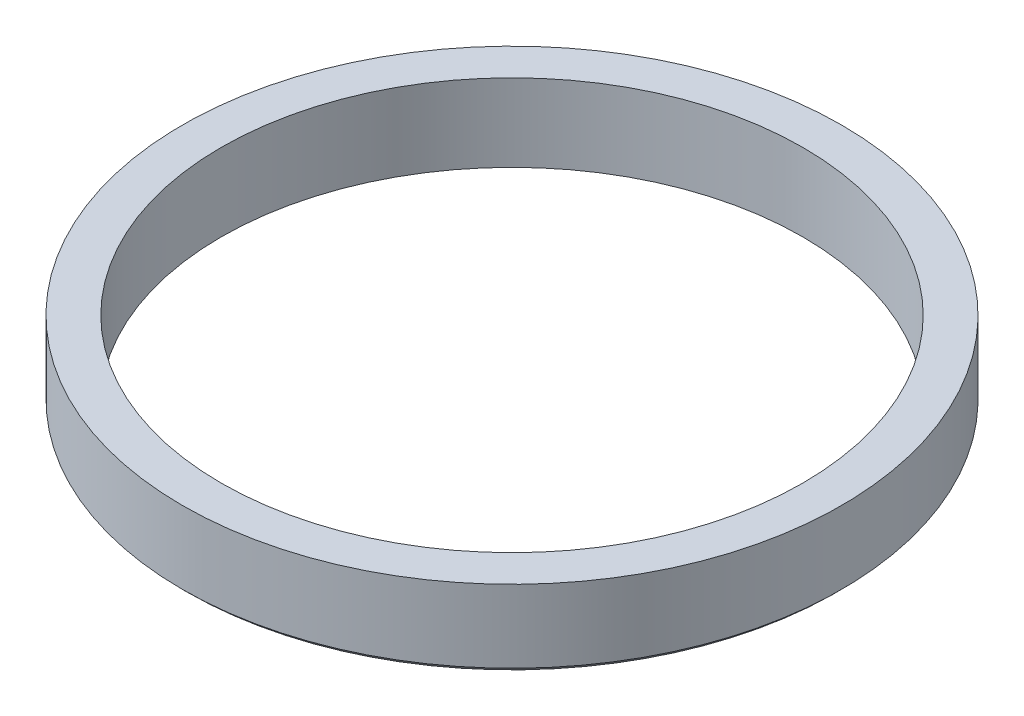
SolidWorks part; units mm, degrees
material "6061-T6 (SS)"
ref_plane "Piano frontale" through (0, 0, 0) normal (0, 0, 1) x (1, 0, 0)
ref_plane "Piano superiore" through (0, 0, 0) normal (0, 1, 0) x (1, 0, 0)
ref_plane "Piano destro" through (0, 0, 0) normal (1, 0, 0) x (0, 0, -1)
sketch "Schizzo1" plane through (0, 0, 0) normal (0, 0, 1) x (1, 0, 0)
  line L0 (0, 0) -> (0, 71.1819) construction
  line L1 (-60, 0) -> (-68, 0)
  line L2 (-68, 0) -> (-68, 16)
  line L3 (-68, 16) -> (-60, 16)
  line L4 (-60, 16) -> (-60, 0)
  dimension "D1" = 120
  dimension "D2" = 136
  dimension "D3" = 16
revolve "Rivoluzione1" add sketch "Schizzo1" angle 360 about L0
chamfer "Smusso1" distance 1 angle 45 1 edges at (0, 0, -68)
